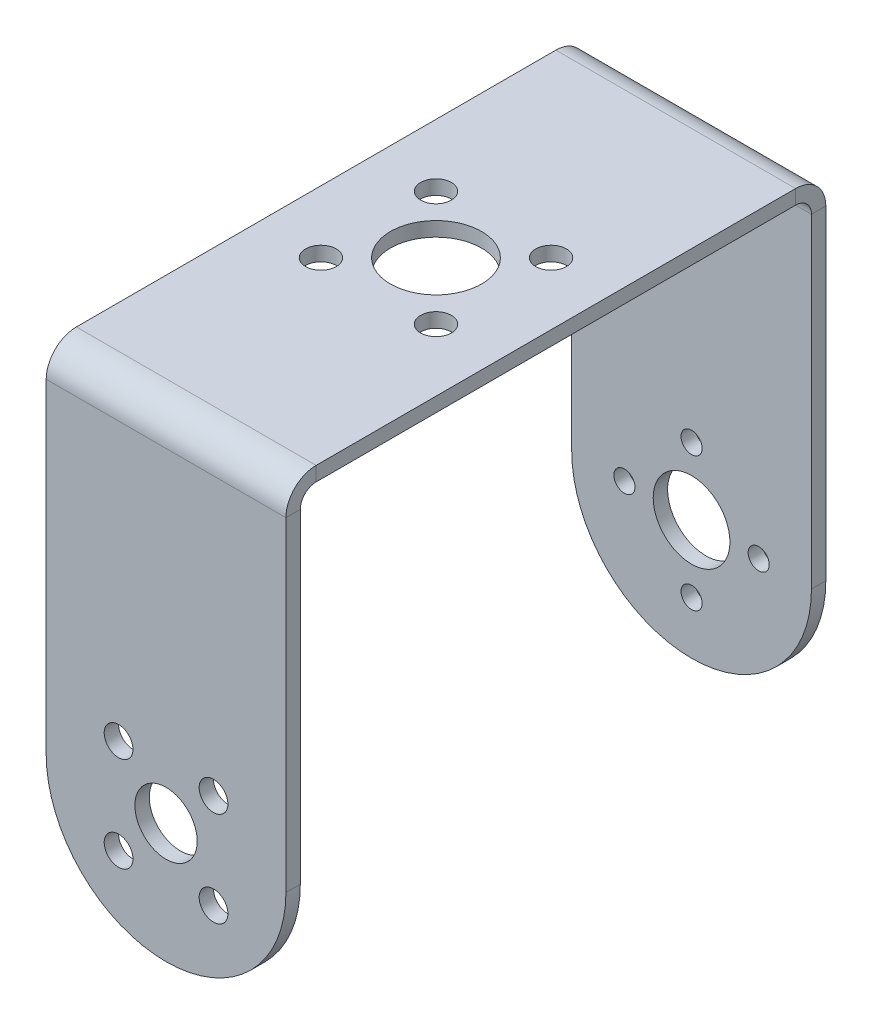
SolidWorks part; units mm, degrees
note: The reader was unsure of these and kept them because the rebuilt part matched: flange length of "Edge-Flange1".
material "1.0037 (S235JR)"
ref_plane "Front Plane" through (0, 0, 0) normal (0, 0, 1) x (1, 0, 0)
ref_plane "Top Plane" through (0, 0, 0) normal (0, 1, 0) x (1, 0, 0)
ref_plane "Right Plane" through (0, 0, 0) normal (1, 0, 0) x (0, 0, -1)
sketch "Sketch1" plane through (0, 0, 0) normal (0, 1, 0) x (1, 0, 0)
  line L1 (12.5, -26.65) -> (-12.5, -26.65)
  line L2 (12.5, -26.65) -> (12.5, 26.65)
  line L3 (12.5, 26.65) -> (-12.5, 26.65)
  line L4 (-12.5, -26.65) -> (-12.5, 26.65)
  line L5 (12.5, -26.65) -> (-12.5, 26.65) construction
  line L6 (12.5, 26.65) -> (-12.5, -26.65) construction
  point P0 (0, 0)
  dimension "D1" = 53.3
  dimension "D2" = 25
base flange "Base-Flange1" sketch "Sketch1" thickness 1.5 reverse thickness direction no parameters "D1"=1.65
edge flange "Edge-Flange1" sketch "Sketch10" flange profiles "Sketch10", "Sketch11" flange angle 90 flange length 48 flange position material outside bend radius 1.65 thickness 1.5 relief rectangular parameters "D1"=2, "D6"=10, "D8"=1
sketch "Sketch10" plane through (0, -1.5, 26.65) normal (0, 0, 1) x (-1, 0, 0)
  line L0 (12.5, 0) -> (-12.5, 0) construction
  line L1 (12.5, 0) -> (-12.5, 0)
  line L2 (-12.5, 0) -> (-12.5, 48)
  line L3 (-12.5, 48) -> (12.5, 48)
  line L4 (12.5, 48) -> (12.5, 0)
sketch "Sketch11" plane through (0, -1.5, -26.65) normal (0, 0, -1) x (1, 0, 0)
  line L0 (12.5, 0) -> (-12.5, 0) construction
  line L1 (12.5, 0) -> (-12.5, 0)
  line L2 (-12.5, 0) -> (-12.5, 48)
  line L3 (-12.5, 48) -> (12.5, 48)
  line L4 (12.5, 48) -> (12.5, 0)
bend "EdgeBend1" bend radius 1.65 bend angle 90 parameters "D5"=1
bend "EdgeBend2" bend radius 1.65 bend angle 90 parameters "D5"=2
sketch "Sketch12" plane through (0, 0, 28.15) normal (0, 0, 1) x (1, 0, 0)
  line L0 (-12.5, -49.5) -> (12.5, -49.5) construction
  line L1 (4.9497, -41.9497) -> (-4.9497, -41.9497) construction
  line L2 (4.9497, -41.9497) -> (4.9497, -32.0503) construction
  line L3 (4.9497, -32.0503) -> (-4.9497, -32.0503) construction
  line L4 (-4.9497, -41.9497) -> (-4.9497, -32.0503) construction
  line L5 (4.9497, -41.9497) -> (-4.9497, -32.0503) construction
  line L6 (4.9497, -32.0503) -> (-4.9497, -41.9497) construction
  circle A0 centre (-4.9497, -32.0503) radius 1.5
  circle A1 centre (4.9497, -32.0503) radius 1.5
  circle A2 centre (-4.9497, -41.9497) radius 1.5
  circle A3 centre (4.9497, -41.9497) radius 1.5
  circle A4 centre (0, -37) radius 3.25
  point P0 (0, -37)
  point P7 (0, -49.5)
  dimension "D3" = 3
  dimension "D4" = 6.5
  dimension "D1" = 14
  dimension "D2" = 12.5
extrude "Cut-Extrude1" cut sketch "Sketch12" against normal up to next normal cut yes
sketch "Sketch13" plane through (0, 0, -28.15) normal (0, 0, -1) x (-1, 0, 0)
  line L0 (0, -37) -> (0, -44) construction
  line L1 (0, -37) -> (-7, -37) construction
  line L2 (0, -37) -> (0, -30) construction
  line L3 (0, -37) -> (7, -37) construction
  circle A0 centre (0, -37) radius 4
  circle A1 centre (0, -44) radius 1.1
  circle A2 centre (-7, -37) radius 1.1
  circle A3 centre (0, -30) radius 1.1
  circle A4 centre (7, -37) radius 1.1
  point P12 (0, -37)
  dimension "D1" = 8
  dimension "D3" = 2.2
  dimension "D2" = 14
  dimension "D4" = 4
extrude "Cut-Extrude2" cut sketch "Sketch13" against normal up to next normal cut yes
fillet "Fillet1" radius 12.5 4 edges at (12.5, -49.5, 27.4) (-12.5, -49.5, 27.4) (-12.5, -49.5, -27.4) (12.5, -49.5, -27.4)
sketch "Sketch17" plane through (0, 0, 0) normal (0, 1, 0) x (1, 0, 0)
  line L1 (6, -6) -> (-6, -6) construction
  line L2 (6, -6) -> (6, 6) construction
  line L3 (6, 6) -> (-6, 6) construction
  line L4 (-6, -6) -> (-6, 6) construction
  line L5 (6, -6) -> (-6, 6) construction
  line L6 (6, 6) -> (-6, -6) construction
  circle A0 centre (-6, 6) radius 1.6
  circle A1 centre (6, 6) radius 1.6
  circle A2 centre (6, -6) radius 1.6
  circle A3 centre (-6, -6) radius 1.6
  point P0 (0, 0)
  dimension "D2" = 3.2
  dimension "D1" = 12
extrude "Cut-Extrude3" cut sketch "Sketch17" against normal through all normal cut yes
sketch "Sketch18" plane through (0, 0, 0) normal (0, 1, 0) x (1, 0, 0)
  circle A0 centre (0, 0) radius 4.75
  dimension "D1" = 9.5
extrude "Cut-Extrude4" cut sketch "Sketch18" against normal through all normal cut yes
sketch "Bend-Lines1" [suppressed] plane through (0, 0, 0) normal (0, 1, 0) x (1, 0, 0)
sketch "Bounding-Box1" [suppressed] plane through (0, 0, 0) normal (0, 1, 0) x (1, 0, 0)
sheet metal parameters "Sheet-Metal1" thickness 1.5 parameters "D1"=2
flat pattern "Flat-Pattern1" [suppressed]
sketch "Bend-Lines2" plane through (0, 0, 0) normal (0, 1, 0) x (1, 0, 0)
sketch3d "Bounding-Box2" [suppressed]
  line L0 (10, 26.25, 0) -> (10, -26.25, 0) construction
  line L1 (-10, 26.25, 0) -> (-10, -26.25, 0) construction
  line L2 (10, 26.25, 0) -> (-10, 26.25, 0) construction
  line L3 (10, -26.25, 0) -> (-10, -26.25, 0) construction
sheet metal parameters "Sheet-Metal2" thickness 1.5 parameters "D1"=2
flat pattern "Flat-Pattern1"
sketch "Bend-Lines2" plane through (0, 0, 0) normal (0, 1, 0) x (1, 0, 0)
  line L0 (10, 26.4098) -> (-10, 26.4098) construction
  line L1 (-10, -26.4098) -> (10, -26.4098) construction
  line L2 (10, 26.4098) -> (-10, 26.4098) construction
  line L3 (-10, -26.4098) -> (10, -26.4098) construction
sketch3d "Bounding-Box2" [suppressed]
  line L0 (-10, 46.5697, 0) -> (-10, -46.5697, 0) construction
  line L1 (10, 46.5697, 0) -> (10, -46.5697, 0) construction
  line L2 (-10, 46.5697, 0) -> (10, 46.5697, 0) construction
  line L3 (-10, -46.5697, 0) -> (10, -46.5697, 0) construction
bend of the flat pattern "EdgeBend1>1"
bend of the flat pattern "EdgeBend2>1"
sheet metal parameters "Sheet-Metal3" thickness 1.5 parameters "D1"=2
flat pattern "Flat-Pattern1"
sketch "Bend-Lines2" plane through (0, 0, 0) normal (0, 1, 0) x (1, 0, 0)
  line L0 (10, 26.4098) -> (-10, 26.4098) construction
  line L1 (-10, -26.4098) -> (10, -26.4098) construction
  line L2 (10, 26.4098) -> (-10, 26.4098) construction
  line L3 (-10, -26.4098) -> (10, -26.4098) construction
sketch3d "Bounding-Box2" [suppressed]
  line L0 (-10, 51.5697, 0) -> (-10, -51.5697, 0) construction
  line L1 (10, 51.5697, 0) -> (10, -51.5697, 0) construction
  line L2 (-10, 51.5697, 0) -> (10, 51.5697, 0) construction
  line L3 (-10, -51.5697, 0) -> (10, -51.5697, 0) construction
bend of the flat pattern "EdgeBend1>1"
bend of the flat pattern "EdgeBend2>1"
sheet metal parameters "Sheet-Metal4" thickness 1.5 parameters "D1"=2
flat pattern "Flat-Pattern1"
sketch "Bend-Lines2" plane through (0, 0, 0) normal (0, 1, 0) x (1, 0, 0)
  line L0 (12.5, 26.4098) -> (-12.5, 26.4098) construction
  line L1 (-12.5, -26.4098) -> (12.5, -26.4098) construction
  line L2 (12.5, 26.4098) -> (-12.5, 26.4098) construction
  line L3 (-12.5, -26.4098) -> (12.5, -26.4098) construction
sketch3d "Bounding-Box2" [suppressed]
  line L0 (-12.5, 71.5696, 0) -> (-12.5, -71.5696, 0) construction
  line L1 (12.5, 71.5696, 0) -> (12.5, -71.5696, 0) construction
  line L2 (-12.5, 71.5696, 0) -> (12.5, 71.5696, 0) construction
  line L3 (-12.5, -71.5696, 0) -> (12.5, -71.5696, 0) construction
bend of the flat pattern "EdgeBend1>1"
bend of the flat pattern "EdgeBend2>1"
sheet metal parameters "Sheet-Metal6" thickness 1.5 parameters "D1"=2
flat pattern "Flat-Pattern1"
sketch "Bend-Lines2" plane through (0, 0, 0) normal (0, 1, 0) x (1, 0, 0)
  line L0 (12.5, 26.885) -> (-12.5, 26.885) construction
  line L1 (-12.5, -26.885) -> (12.5, -26.885) construction
  line L2 (12.5, 26.885) -> (-12.5, 26.885) construction
  line L3 (-12.5, -26.885) -> (12.5, -26.885) construction
sketch3d "Bounding-Box2" [suppressed]
  line L0 (-12.5, 75.1199, 0) -> (-12.5, -75.1199, 0) construction
  line L1 (12.5, 75.1199, 0) -> (12.5, -75.1199, 0) construction
  line L2 (-12.5, 75.1199, 0) -> (12.5, 75.1199, 0) construction
  line L3 (-12.5, -75.1199, 0) -> (12.5, -75.1199, 0) construction
bend of the flat pattern "EdgeBend2>2"
bend of the flat pattern "EdgeBend1>2"
sheet metal parameters "Sheet-Metal7" thickness 1.5 parameters "D1"=2
flat pattern "Flat-Pattern1"
sketch "Bend-Lines2" plane through (0, 0, 0) normal (0, 1, 0) x (1, 0, 0)
  line L0 (12.5, 26.885) -> (-12.5, 26.885) construction
  line L1 (-12.5, -26.885) -> (12.5, -26.885) construction
  line L2 (12.5, 26.885) -> (-12.5, 26.885) construction
  line L3 (-12.5, -26.885) -> (12.5, -26.885) construction
sketch3d "Bounding-Box2" [suppressed]
  line L0 (-12.5, 75.1199, 0) -> (-12.5, -75.1199, 0) construction
  line L1 (12.5, 75.1199, 0) -> (12.5, -75.1199, 0) construction
  line L2 (-12.5, 75.1199, 0) -> (12.5, 75.1199, 0) construction
  line L3 (-12.5, -75.1199, 0) -> (12.5, -75.1199, 0) construction
bend of the flat pattern "EdgeBend2>2"
bend of the flat pattern "EdgeBend1>2"
